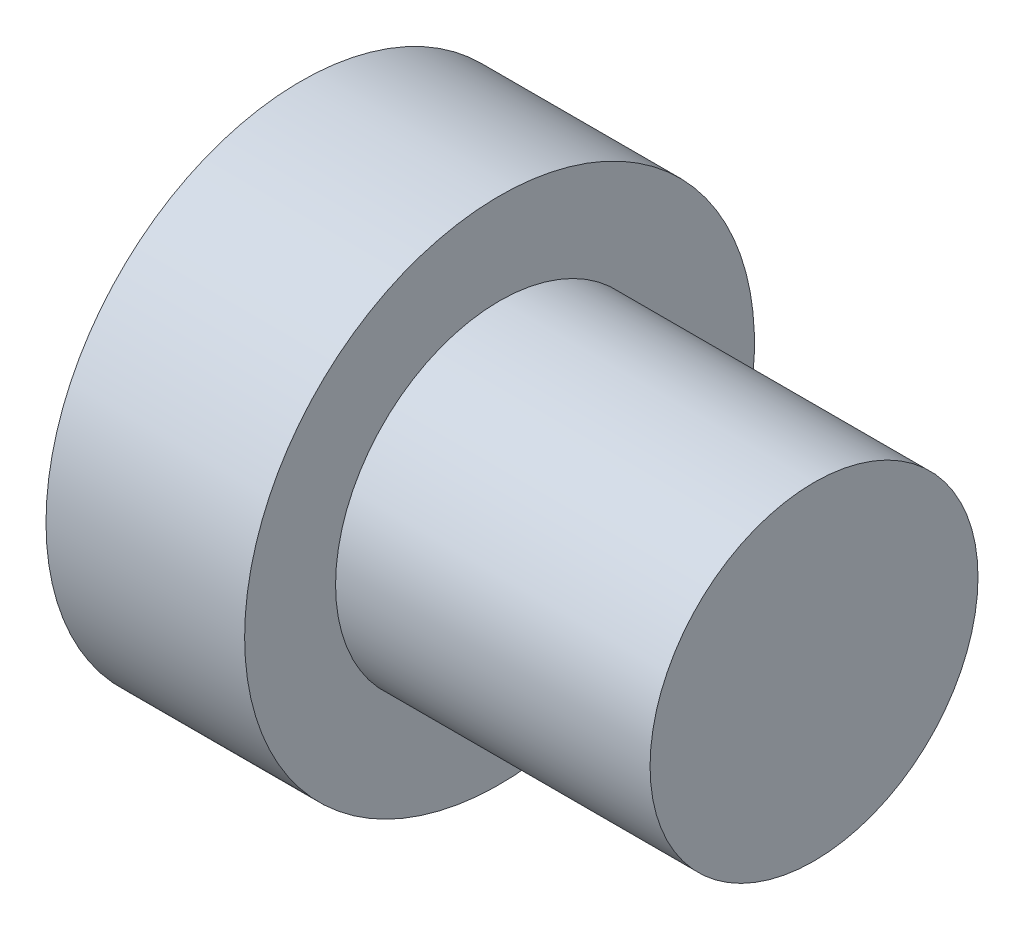
SolidWorks part; units mm, degrees
ref_plane "Front Plane" through (0, 0, 0) normal (0, 0, 1) x (1, 0, 0)
ref_plane "Top Plane" through (0, 0, 0) normal (0, 1, 0) x (1, 0, 0)
ref_plane "Right Plane" through (0, 0, 0) normal (1, 0, 0) x (0, 0, -1)
sketch "Plug_ORB4 Sketch" plane through (0, 0, 0) normal (0, 0, 1) x (1, 0, 0)
  line L0 (-1000, 0) -> (1000, 0) construction
  line L1 (9.5, 0) -> (9.5, 4.953)
  line L2 (9.5, 4.953) -> (0, 4.953)
  line L3 (0, 4.953) -> (0, 7.7)
  line L4 (0, 7.7) -> (-6, 7.7)
  line L5 (-6, 7.7) -> (-6, 0)
  line L6 (-6, 0) -> (9.5, 0)
revolve "Plug_ORB4" add sketch "Plug_ORB4 Sketch" angle 360 about L0
ref_axis "Engine Axis" through (10.275, 0, 0) along (-1, 0, 0)
